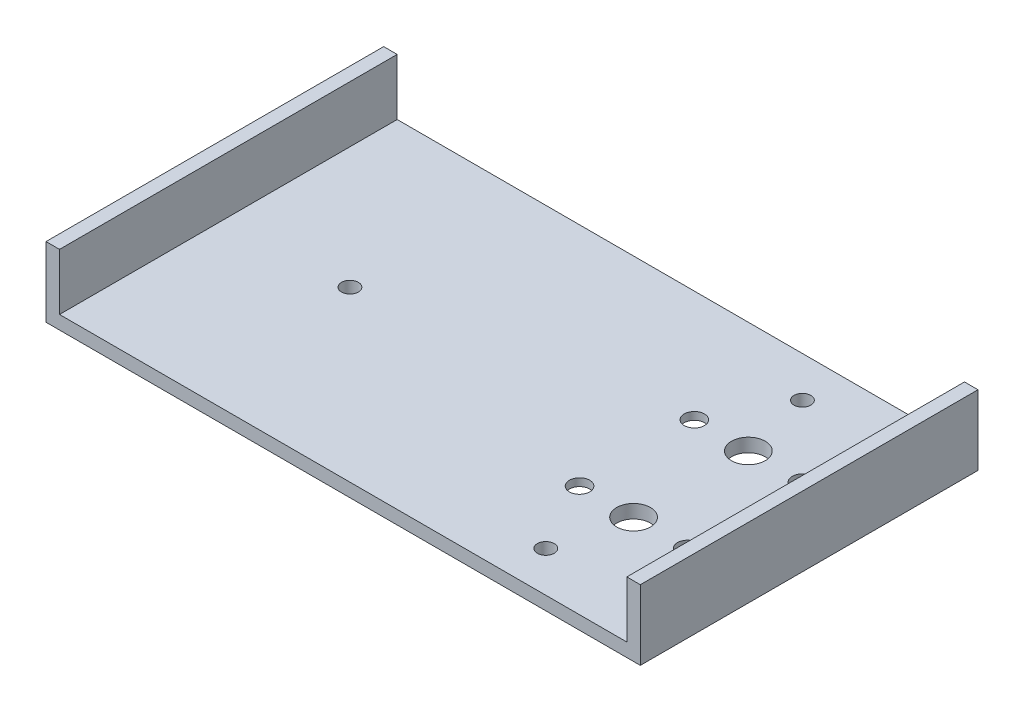
SolidWorks part; units mm, degrees
ref_plane "Спереди" through (0, 0, 0) normal (0, 0, 1) x (1, 0, 0)
ref_plane "Сверху" through (0, 0, 0) normal (0, 1, 0) x (1, 0, 0)
ref_plane "Справа" through (0, 0, 0) normal (1, 0, 0) x (0, 0, -1)
sketch "Эскиз1" plane through (0, 0, 0) normal (0, 0, 1) x (1, 0, 0)
  line L1 (0, 0) -> (176, 0)
  line L3 (4, 4) -> (172, 4)
  line L5 (176, 0) -> (176, 20.7)
  line L6 (0, 0) -> (0, 20.7)
  line L7 (0, 20.7) -> (4, 20.7)
  line L8 (4, 4) -> (4, 20.7)
  line L9 (176, 20.7) -> (172, 20.7)
  line L10 (172, 4) -> (172, 20.7)
  dimension "D1" = 176
  dimension "D2" = 4
  dimension "D3" = 4
  dimension "D4" = 20.7
  dimension "D5" = 4
  dimension "D6" = 20.7
extrude "Бобышка-Вытянуть1" add sketch "Эскиз1" along normal blind 100
sketch "Эскиз2" plane through (0, 0, 0) normal (0, -1, 0) x (1, 0, 0)
  line L0 (141, 100) -> (141, 0) construction
  line L1 (0, 100) -> (176, 100) construction
  line L2 (176, 100) -> (176, 0) construction
  line L3 (176, 50) -> (0, 50) construction
  line L4 (0, 100) -> (0, 0) construction
  line L5 (176, 88) -> (95.8123, 88) construction
  line L6 (176, 12) -> (95.5195, 12) construction
  line L7 (0, 0) -> (176, 0) construction
  line L8 (155.9807, 67) -> (108.093, 67) construction
  line L9 (154.9902, 33) -> (107.2674, 33) construction
  circle A0 centre (141, 67) radius 5
  circle A1 centre (141, 33) radius 5
  circle A2 centre (40, 50) radius 2.5
  circle A3 centre (166, 88) radius 2.5
  circle A4 centre (136, 88) radius 2.5
  circle A5 centre (166, 12) radius 2.5
  circle A6 centre (136, 12) radius 2.5
  circle A7 centre (157, 33) radius 3
  circle A8 centre (125, 33) radius 3
  circle A9 centre (157, 67) radius 3
  circle A10 centre (125, 67) radius 3
  dimension "D2" = 10
  dimension "D3" = 10
  dimension "D6" = 5
  dimension "D8" = 5
  dimension "D9" = 5
  dimension "D14" = 5
  dimension "D15" = 5
  dimension "D18" = 6
  dimension "D19" = 6
  dimension "D20" = 6
  dimension "D21" = 6
  dimension "D1" = 35
  dimension "D4" = 34
  dimension "D5" = 17
  dimension "D7" = 40
  dimension "D10" = 10
  dimension "D11" = 30
  dimension "D12" = 12
  dimension "D13" = 12
  dimension "D16" = 10
  dimension "D17" = 30
  dimension "D22" = 16
  dimension "D23" = 16
  dimension "D24" = 16
  dimension "D25" = 16
extrude "Вырез-Вытянуть1" cut sketch "Эскиз2" against normal blind 4
chamfer "Фаска3" distance 3 angle 30 1 edges at (157, 0, 64) first distance on face at (125, 0, 64)
chamfer "Фаска4" distance 3 angle 30 1 edges at (125, 0, 64) first distance on face at (157, 0, 73)
chamfer "Фаска5" distance 3 angle 30 1 edges at (125, 0, 30) first distance on face at (125, 0, 73)
chamfer "Фаска6" distance 3 angle 30 1 edges at (157, 0, 30) first distance on face at (125, 0, 39)
